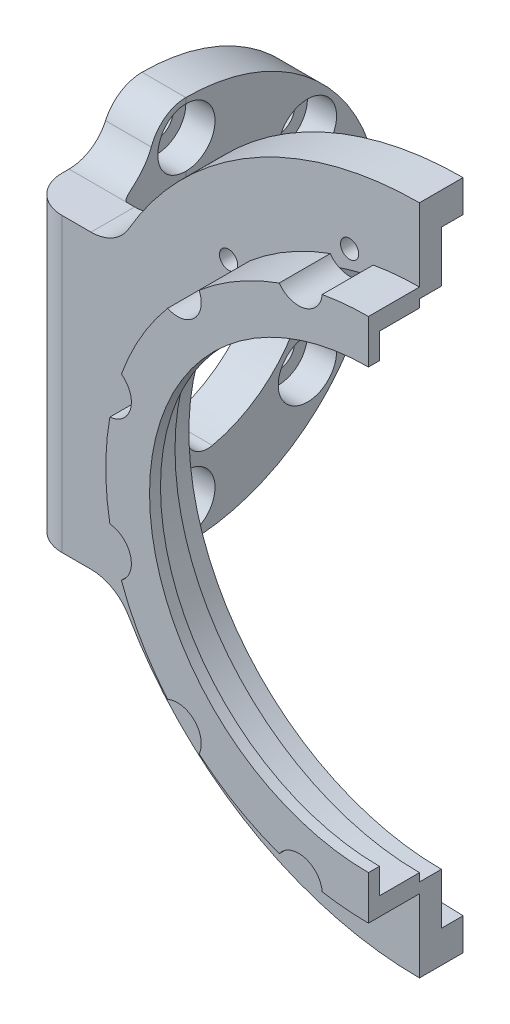
SolidWorks part; units mm, degrees
ref_plane "前视基准面" through (0, 0, 0) normal (0, 0, 1) x (1, 0, 0)
ref_plane "上视基准面" through (0, 0, 0) normal (0, 1, 0) x (1, 0, 0)
ref_plane "右视基准面" through (0, 0, 0) normal (1, 0, 0) x (0, 0, -1)
sketch "草图3" plane through (0, 0, 0) normal (0, 0, 1) x (1, 0, 0)
  circle A0 centre (0, 0) radius 34.6
  circle A1 centre (0, 0) radius 46
extrude "凸台-拉伸2" add sketch "草图3" along normal blind 3
ref_plane "基准面5" through (0, 0, 3) normal (0, 0, 1) x (1, 0, 0)
sketch "草图5" plane through (0, 0, 3) normal (0, 0, 1) x (1, 0, 0)
  circle A0 centre (0, 0) radius 33.5
  circle A1 centre (0, 0) radius 36
extrude "凸台-拉伸3" add sketch "草图5" along normal blind 5.49
sketch "草图2" plane through (0, 0, 0) normal (0, 0, 1) x (1, 0, 0)
  circle A0 centre (0, 0) radius 41.6
  circle A1 centre (0, 0) radius 46
extrude "凸台-拉伸1" add sketch "草图2" against normal blind 2.98
sketch "草图6" plane through (0, 0, 8.49) normal (0, 0, 1) x (1, 0, 0)
  circle A0 centre (0, 0) radius 30
  circle A1 centre (0, 0) radius 36
extrude "凸台-拉伸4" add sketch "草图6" along normal blind 1.5
sketch "草图8" plane through (0, 0, 0) normal (0, 0, 1) x (1, 0, 0)
  line L6 (-50, 20.008) -> (-45.0139, 20.008)
  line L8 (7.1335, 0) -> (-7.1335, 0) construction
  line L10 (-50, 20.008) -> (-50, -20.008)
  line L11 (-50, -20.008) -> (-45.0139, -20.008)
  arc A16 (-45.0139, 20.008) -> (-39.8396, 22.9958) centre (-45.0139, 25.9824) ccw
  arc A17 (-39.8396, 22.9958) -> (-39.8396, -22.9958) centre (0, 0) ccw
  arc A19 (-45.0139, -20.008) -> (-39.8396, -22.9958) centre (-45.0139, -25.9824) cw
extrude "凸台-拉伸5" add sketch "草图8" along normal blind 3 and the other way blind 2.98
hole_wizard "M3 螺纹孔的螺纹孔钻头1" positions "3D草图3" profile "草图12" hole size "M3" standard "ISO" end condition through all
sketch3d "3D草图3"
  line L2 (0, 0, 0) -> (0, 37, 0)
  line L3 (0, 0, 0) -> (11.5811, 0, 0)
  point P55 (9.5763, 35.7393, 3)
  point P76 (26.163, 26.163, 3)
  point P83 (35.7393, 9.5763, 3)
  point P96 (-35.7393, 9.5763, 3)
  point P97 (-26.163, 26.163, 3)
  point P98 (-9.5763, 35.7393, 3)
  point P99 (35.7393, -9.5763, 3)
  point P100 (26.163, -26.163, 3)
  point P101 (9.5763, -35.7393, 3)
  point P102 (-9.5763, -35.7393, 3)
  point P103 (-26.163, -26.163, 3)
  point P104 (-35.7393, -9.5763, 3)
sketch "草图12" plane through (-35.7393, -9.5763, 3) normal (1, 0, 0) x (0, -1, 0)
  line L0 (0, 0) -> (0, 5.98)
  line L1 (0, 5.98) -> (1.25, 5.98)
  line L2 (1.25, 5.98) -> (1.25, 0)
  line L5 (1.25, 0) -> (0, 0)
  line L11 (0, -6.35) -> (0, 107.95) construction
  dimension "通孔孔直径" = 2.5
  dimension "通孔孔深度" = 5.98
sketch "草图13" plane through (0, 0, 3) normal (0, 0, 1) x (1, 0, 0)
  line L0 (0, 0) -> (0, 10.9464)
  line L1 (0, 0) -> (8.3109, 0)
  circle A0 centre (-35.7393, 9.5763) radius 1.25
  circle A1 centre (-26.163, 26.163) radius 2.2
  circle A2 centre (-9.5763, 35.7393) radius 2.2
  circle A3 centre (-9.5763, -35.7393) radius 2.2
  circle A4 centre (-26.163, -26.163) radius 2.2
  circle A5 centre (-35.7393, -9.5763) radius 1.25
  circle A6 centre (9.5763, -35.7393) radius 2.2
  circle A7 centre (26.163, -26.163) radius 2.2
  circle A8 centre (9.5763, 35.7393) radius 2.2
  circle A9 centre (26.163, 26.163) radius 2.2
  circle A10 centre (35.7393, -9.5763) radius 1.25
  circle A11 centre (35.7393, 9.5763) radius 1.25
extrude "切除-拉伸1" cut sketch "草图13" along normal up to next contours A5 | A4 | A0 | A1 | A2 | A9 | A11 | A10 | A6 | A3 | A8 | A7 region at (-35.7393, 9.5763, 3) region at (-26.163, 26.163, 3) region at (-9.5763, 35.7393, 3) region at (-9.5763, -35.7393, 3) region at (-26.163, -26.163, 3) region at (-35.7393, -9.5763, 3) region at (9.5763, -35.7393, 3) region at (26.163, 26.163, 3) region at (35.7393, -9.5763, 3) region at (35.7393, 9.5763, 3)
sketch "草图25" plane through (0, 0, 3) normal (0, 0, 1) x (1, 0, 0)
  circle A0 centre (-9.5763, 35.7393) radius 3.25
  circle A1 centre (-26.163, 26.163) radius 3.25
  circle A2 centre (-35.7393, 9.5763) radius 3.25
  circle A3 centre (-35.7393, -9.5763) radius 3.25
  circle A4 centre (-26.163, -26.163) radius 3.25
  circle A5 centre (-9.5763, -35.7393) radius 3.25
extrude "切除-拉伸9" cut sketch "草图25" along normal blind 10
ref_plane "基准面6" through (-50, 0, 0) normal (-1, 0, 0) x (0, 0, 1)
sketch "草图26" plane through (-50, 0, 0) normal (-1, 0, 0) x (0, 0, 1)
  line L1 (-2.98, -20.008) -> (3, -20.008)
  line L5 (3, 20.008) -> (3, -20.008) construction
  line L6 (-2.98, 20.008) -> (3, 20.008)
  line L7 (3, 12.2277) -> (3, 23.2096) construction
  line L8 (3, 20.008) -> (3, -20.008)
  line L9 (-2.98, -20.008) -> (3, -20.008)
  arc A8 (-12.98, 26.5) -> (-12.98, -26.5) centre (-12.98, 0) ccw
  arc A9 (-12.98, 26.5) -> (-7.98, 23.254) centre (-12.98, 21.0261) cw
  arc A10 (-2.98, 20.008) -> (-7.98, 23.254) centre (-2.98, 25.4819) cw
  arc A11 (-2.98, -20.008) -> (-7.98, -23.254) centre (-2.98, -25.4819) ccw
  arc A12 (-12.98, -26.5) -> (-7.98, -23.254) centre (-12.98, -21.0261) ccw
extrude "凸台-拉伸7" add sketch "草图26" along normal blind 4 and the other way blind 2 contours A8 A12 A11 L1 L8 L6 A10 A9 region at (-50, 0, -16.9157)
sketch "草图27" plane through (0, 0, 0) normal (0, 0, 1) x (1, 0, 0)
  line L0 (0, 0) -> (0, 46)
  line L1 (0, -46) -> (0, 0)
  arc A0 (-39.8396, -22.9958) -> (-39.8396, 22.9958) centre (0, 0) ccw construction
  arc A1 (0, 46) -> (0, -46) centre (0, 0) cw
extrude "切除-拉伸10" cut sketch "草图27" against normal through all both and the other way through all
hole_wizard "M4 六角凹头盖的柱孔3" positions "3D草图5" profile "草图29" counterbore size "M4" standard "BSI" end condition up to next
sketch3d "3D草图5"
  point P0 (-48, 21.75, -12.98)
  point P4 (-48, 13.9806, -29.6415)
  point P28 (-48, -13.9806, -29.6415)
  point P29 (-48, -21.75, -12.98)
sketch "草图29" plane through (-48, 21.75, -12.98) normal (0, 1, 0) x (0, 0, -1)
  line L0 (0, 0) -> (0, 6)
  line L1 (0, 6) -> (2.25, 6)
  line L3 (2.25, 6) -> (2.25, 4)
  line L4 (2.25, 4) -> (4, 4)
  line L5 (4, 4) -> (4, 0)
  line L7 (4, 0) -> (0, 0)
  line L11 (0, -6.35) -> (0, 107.95) construction
  dimension "通孔孔直径" = 4.5
  dimension "通孔孔深度" = 6
  dimension "柱形沉头孔直径" = 8
  dimension "柱形沉头孔深度" = 4
fillet "圆角1" radius 5 1 edges at (-54, 0, 3)
sketch "草图30" plane through (-50, 0, 0) normal (-1, 0, 0) x (0, 0, 1)
  line L1 (-12.98, 17) -> (-12.98, -17)
  arc A7 (-12.98, -17) -> (-12.98, 17) centre (-12.98, 0) cw
extrude "切除-拉伸11" cut sketch "草图30" along normal blind 10 and the other way blind 10
fillet "圆角2" radius 3 2 edges at (-51, -17, -12.98) (-51, 17, -12.98)
fillet "圆角4" radius 2 1 edges at (-48, 0, -2.98) second distance 10 first distance on face at (-31.2671, 0, -2.98)
